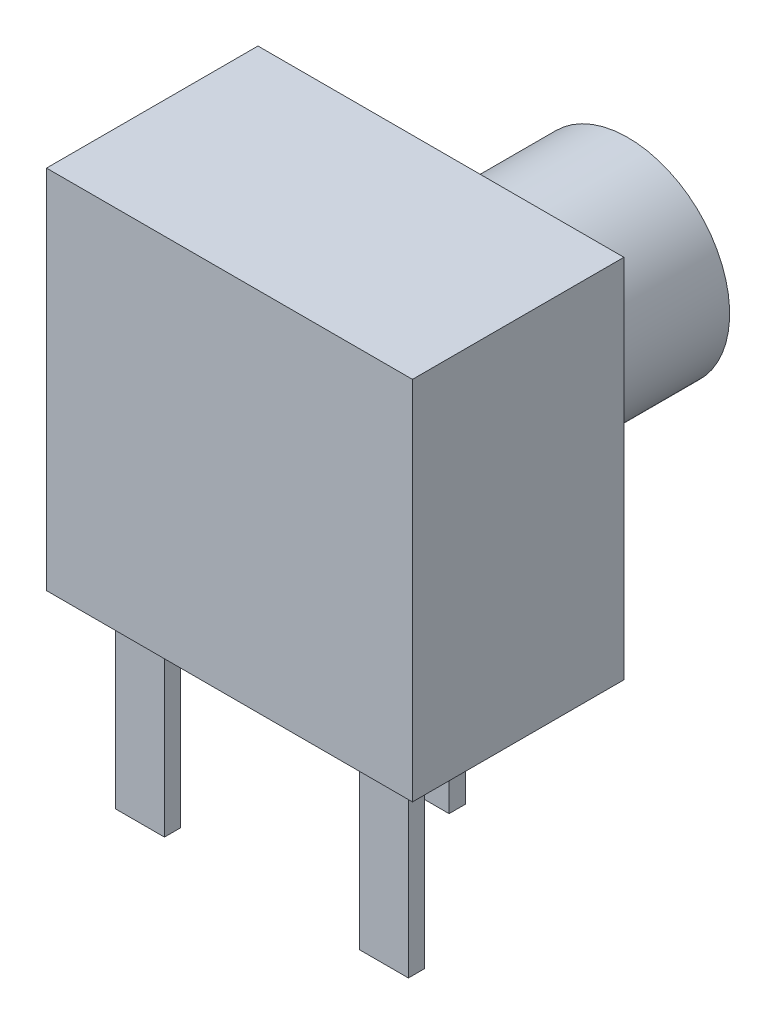
SolidWorks part; units mm, degrees
ref_plane "Front" through (0, 0, 0) normal (0, 0, 1) x (1, 0, 0)
ref_plane "Top" through (0, 0, 0) normal (0, 1, 0) x (1, 0, 0)
ref_plane "Right" through (0, 0, 0) normal (1, 0, 0) x (0, 0, -1)
sketch "草图1" plane through (0, 0, 0) normal (0, 0, 1) x (1, 0, 0)
  line L0 (-7.2712, 0) -> (11.8328, 0) construction
  line L1 (-2.25, 2.25) -> (2.25, 2.25)
  line L2 (-2.25, 2.25) -> (-2.25, -2.25)
  line L3 (-2.25, -2.25) -> (2.25, -2.25)
  line L4 (2.25, 2.25) -> (2.25, -2.25)
  line L5 (0, 3.2998) -> (0, -4.1098) construction
  dimension "D1" = 4.5
  dimension "D2" = 4.5
extrude "凸台-拉伸1" add sketch "草图1" along normal blind 2.6
ref_point "点1"
sketch "草图3" plane through (0, 0, 0) normal (0, 0, -1) x (-1, 0, 0)
  circle A0 centre (0, 0) radius 1.25
  dimension "D1" = 2.5
extrude "凸台-拉伸2" add sketch "草图3" along normal blind 2.3
sketch "草图4" plane through (0, -2.25, 0) normal (0, -1, 0) x (1, 0, 0)
  line L0 (-2.25, 0) -> (2.25, 0) construction
  line L1 (0.3, 0) -> (-0.3, 0)
  line L2 (0.3, 0) -> (0.3, 0.2)
  line L3 (0.3, 0.2) -> (-0.3, 0.2)
  line L4 (-0.3, 0) -> (-0.3, 0.2)
  line L5 (0, 0) -> (0, 2.9208) construction
  line L6 (2.25, 2.6) -> (2.25, 0) construction
  line L7 (1.8, 2) -> (1.2, 2)
  line L8 (1.8, 2) -> (1.8, 2.2)
  line L9 (1.8, 2.2) -> (1.2, 2.2)
  line L10 (1.2, 2) -> (1.2, 2.2)
  line L11 (-1.2, 2) -> (-1.8, 2)
  line L12 (-1.2, 2) -> (-1.2, 2.2)
  line L13 (-1.2, 2.2) -> (-1.8, 2.2)
  line L14 (-1.8, 2) -> (-1.8, 2.2)
  line L15 (-2.25, 2.6) -> (-2.25, 0) construction
  dimension "D1" = 0.2
  dimension "D2" = 0.6
  dimension "D3" = 0.2
  dimension "D4" = 0.6
  dimension "D5" = 0.45
  dimension "D6" = 2
  dimension "D7" = 0.45
  dimension "D8" = 2
  dimension "D9" = 0.2
  dimension "D10" = 0.6
extrude "凸台-拉伸3" add sketch "草图4" along normal blind 2.3
ref_point "点2"
ref_axis "基准轴1" through (1.5, -4.55, 2.1) along (0, -1, 0)
